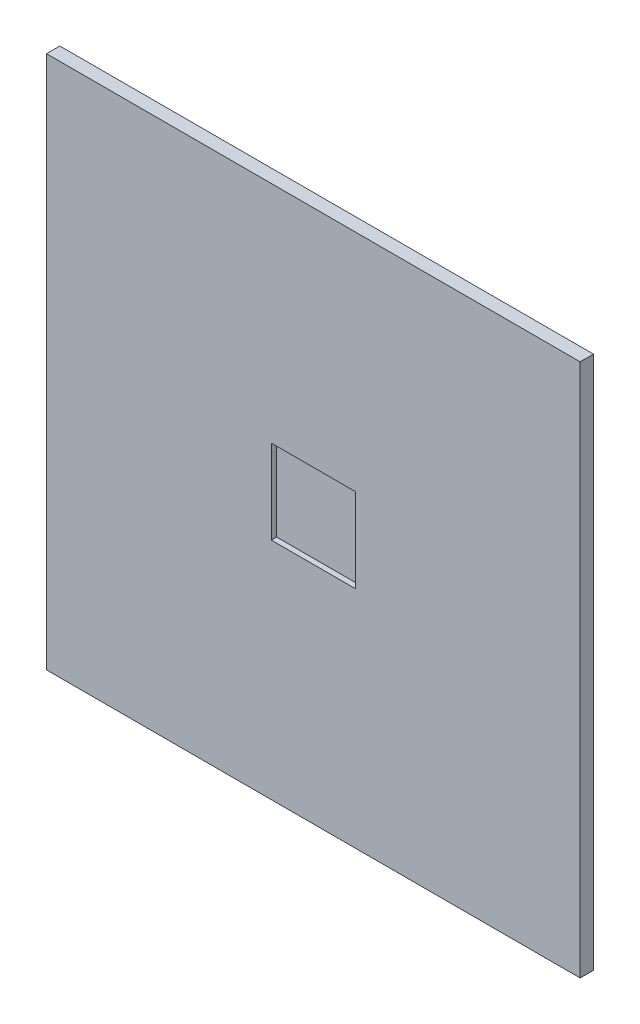
SolidWorks part; units mm, degrees
ref_plane "Front Plane" through (0, 0, 0) normal (0, 0, 1) x (1, 0, 0)
ref_plane "Top Plane" through (0, 0, 0) normal (0, 1, 0) x (1, 0, 0)
ref_plane "Right Plane" through (0, 0, 0) normal (1, 0, 0) x (0, 0, -1)
sketch "Sketch1" plane through (0, 0, 0) normal (0, 0, 1) x (1, 0, 0)
  line L0 (20, 20) -> (-20, -20) construction
  line L1 (-20, -20) -> (20, -20)
  line L2 (-20, -20) -> (-20, 20)
  line L3 (-20, 20) -> (20, 20)
  line L4 (20, -20) -> (20, 20)
  line L5 (-20, 20) -> (20, -20) construction
  line L6 (-3.15, 3.15) -> (3.15, -3.15) construction
  line L7 (-3.15, -3.15) -> (3.15, -3.15)
  line L8 (-3.15, -3.15) -> (-3.15, 3.15)
  line L9 (-3.15, 3.15) -> (3.15, 3.15)
  line L10 (3.15, -3.15) -> (3.15, 3.15)
  line L11 (3.15, 3.15) -> (-3.15, -3.15) construction
  point P0 (0, 0)
  point P6 (0, 0)
  point P11 (0, 0)
  point P14 (0, 0)
  dimension "D1" = 40
  dimension "D2" = 40
  dimension "D3" = 6.3
  dimension "D4" = 6.3
extrude "Boss-Extrude1" add sketch "Sketch1" along normal blind 1 contours L1 L4 L3 L2 L10 L7 L8 L9 | L7 L10 L9 L8 region at (-19.4343, 0, 0) region at (0, 0, 0)
extrude "PCB" cut sketch "Sketch1<3>" against normal blind 0.4 from surface contours L7 L10 L9 L8 region at (0, 0, 0) starting at face at (0, 0, 1)
sketch "Sketch1<3>" plane through (0, 0, 0) normal (0, 0, 1) x (1, 0, 0) same geometry as "Sketch1"
equation "\"pcb_length\"= 40 ' length of the chip in the direction of the feadline"
equation "\"pcb_side\"= 40    ' length of the chip in the other direction"
equation "\"pcb_width\"= 1"
equation "\"wall_width\"= 1  ' minimal width from the box walls"
equation "\"route_width\"= 1 ' The width of the trace on the lid for not touching the signal roates."
equation "\"route_clearence\"= 0.4 ' The clearence depth of the trace on the lid for not touching the signal roates."
equation "\"route_chip_clearence\"= 1"
equation "\"port_count\"= 6"
equation "\"port_space\"= 1.5"
equation "\"port_length\"= 5.1"
equation "\"port_width\"= 5.1"
equation "\"chip_length\"= 6.3 ' length of the chip in the direction of the feadline"
equation "\"chip_side\"= 6.3 ' length of the chip in the other direction"
equation "\"pedestal_depth\"= 2 ' depth of the pedestal under the chip"
equation "\"chip_leg\"= 0.8  ' size of the legs the chip lay on in case there is pedestal"
equation "\"wing_length\"= 10 ' Mounting wing size"
equation "\"wing_width\"= 1 ' mounting wing width"
equation "\"bonding_clearence\"= 1"
equation "\"box_height\"= \"wall_width\" + \"pedestal_depth\" + \"pcb_width\""
equation "\"box_length\"= \"pcb_length\" + 2 * \"wall_width\""
equation "\"box_side\"= \"pcb_side\" + 2 * \"wall_width\""
equation "\"D1@Sketch1\"=\"pcb_length\""
equation "\"D2@Sketch1\"=\"pcb_side\""
equation "\"D3@Sketch1\"=\"chip_length\""
equation "\"D1@Boss-Extrude1\"=\"pcb_width\""
equation "\"chip_width\"= 0.4 ' width of the chip"
equation "\"D1@PCB\"=\"chip_width\""
